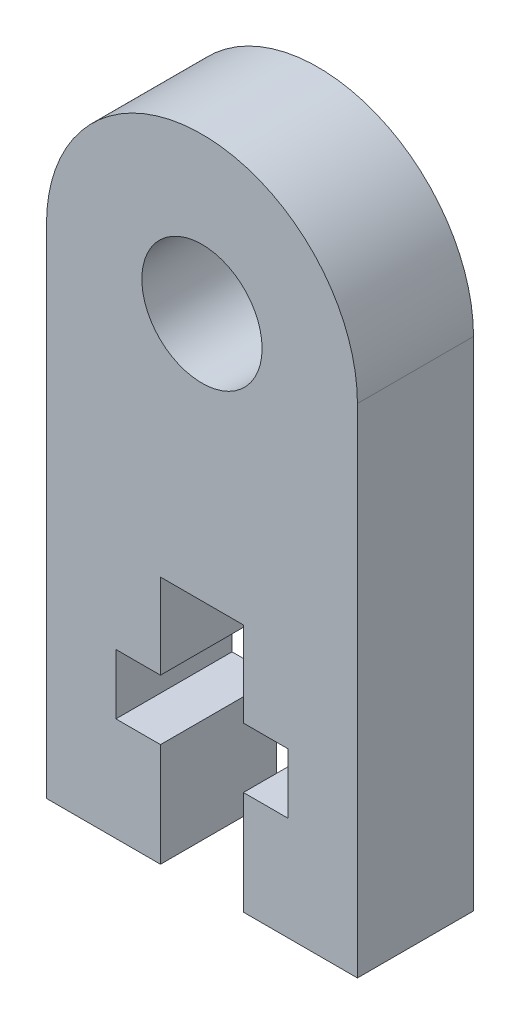
SolidWorks part; units mm, degrees
ref_plane "Front Plane" through (0, 0, 0) normal (0, 0, 1) x (1, 0, 0)
ref_plane "Top Plane" through (0, 0, 0) normal (0, 1, 0) x (1, 0, 0)
ref_plane "Right Plane" through (0, 0, 0) normal (1, 0, 0) x (0, 0, -1)
sketch "Sketch1" plane through (0, 0, 0) normal (0, 0, 1) x (1, 0, 0)
  line L0 (0, 0) -> (-2.0506, 2.0506) construction
  line L1 (0, 0) -> (0, 2.9) construction
  line L2 (-7.5, 0) -> (-7.5, -24)
  line L3 (-7.5, -24) -> (7.5, -24)
  line L4 (7.5, -24) -> (7.5, 0)
  line L5 (0, 0) -> (0, -24) construction
  circle A0 centre (0, 0) radius 2.9
  arc A1 (-7.5, 0) -> (7.5, 0) centre (0, 0) cw
  dimension "D1" = 5.8
  dimension "D4" = 45
  dimension "D5" = 24
  dimension "D6" = 15
extrude "Boss-Extrude1" add sketch "Sketch1" along normal blind 5.6
sketch "Sketch3" plane through (0, 0, 5.6) normal (0, 0, 1) x (1, 0, 0)
  line L0 (-7.5, -24) -> (7.5, -24) construction
  line L1 (-2, -24) -> (2, -24)
  line L2 (-2, -24) -> (-2, -19)
  line L3 (-2, -12) -> (2, -12)
  line L4 (2, -24) -> (2, -19)
  line L5 (0, -12) -> (0, 0) construction
  line L6 (2, -16.1) -> (4.15, -16.1)
  line L7 (-4.15, -16.1) -> (-2, -16.1)
  line L8 (-4.15, -16.1) -> (-4.15, -19)
  line L9 (-4.15, -19) -> (-2, -19)
  line L10 (4.15, -16.1) -> (4.15, -19)
  line L11 (-2, -16.1) -> (-2, -12)
  line L12 (2, -19) -> (4.15, -19)
  line L13 (2, -16.1) -> (2, -12)
  point P18 (-3.075, -19)
  dimension "D1" = 4
  dimension "D3" = 12
  dimension "D4" = 8.3
  dimension "D5" = 2.9
  dimension "D6" = 5
extrude "Cut-Extrude2" cut sketch "Sketch3" against normal through all
equation "\"smallPulleyTeeth\"= 15"
equation "\"largePulleyTeeth\"= 30"
equation "\"eighthThick\"= 2.9mm"
equation "\"sixteenthThick\" = 1.7mm"
equation "\"quarterThick\"=5.6mm"
equation "\"OD\" = 150mm"
equation "\"puckAngle\" = 60.5deg"
equation "\"puckDiam\" = 76.5mm"
equation "\"axlePress\" = 5.8mm"
equation "\"D1@Sketch1\"=\"axlePress\""
equation "\"D1@Boss-Extrude1\"=\"quarterThick\""
equation "\"press\" = 0.2mm"
equation "\"wheelClear\" = 0.3mm"
equation "\"10-32clear\" = 4.5mm"
equation "\"D1@Sketch3\"=\"8-32clear\""
equation "\"6-32clear\" = 3.3mm"
equation "\"8-32clear\" = 4.0mm"
equation "\"wheelHeight\" = 24mm"
equation "\"D5@Sketch1\"=\"wheelHeight\""
